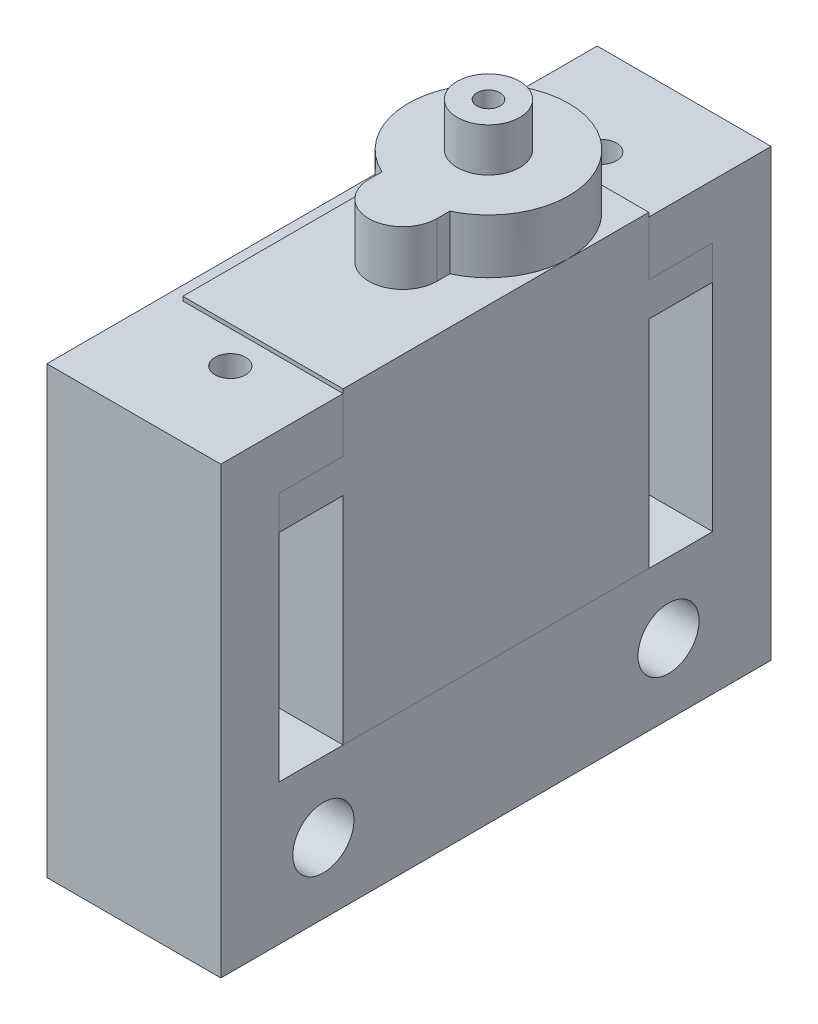
SolidWorks part; units mm, degrees
ref_plane "Plan de face" through (0, 0, 0) normal (0, 0, 1) x (1, 0, 0)
ref_plane "Plan de dessus" through (0, 0, 0) normal (0, 1, 0) x (1, 0, 0)
ref_plane "Plan de droite" through (0, 0, 0) normal (1, 0, 0) x (0, 0, -1)
sketch "Esquisse1" plane through (0, 0, 0) normal (1, 0, 0) x (0, 0, -1)
  line L0 (11.25, 0) -> (-11.25, 0) construction
  line L1 (0, 14.95) -> (0, -14.95) construction
  line L2 (-11.25, -14.95) -> (11.25, -14.95)
  line L3 (11.25, -14.95) -> (11.25, 0.95)
  line L4 (11.25, 0.95) -> (15.95, 0.95)
  line L5 (15.95, 0.95) -> (15.95, 3.45)
  line L6 (15.95, 3.45) -> (11.25, 3.45)
  line L7 (11.25, 3.45) -> (11.25, 7.75)
  line L8 (11.25, 7.75) -> (-11.25, 7.75)
  line L9 (-11.25, 7.75) -> (-11.25, 3.45)
  line L10 (-11.25, 3.45) -> (-15.95, 3.45)
  line L11 (-15.95, 3.45) -> (-15.95, 0.95)
  line L12 (-15.95, 0.95) -> (-11.25, 0.95)
  line L13 (-11.25, 0.95) -> (-11.25, -14.95)
  point P4 (0, 0)
  point P8 (0, 0)
  dimension "D1" = 15.9
  dimension "D2" = 2.5
  dimension "D3" = 4.7
  dimension "D4" = 22.5
  dimension "D5" = 4.7
  dimension "D6" = 4.3
  dimension "D7" = 2.5
  dimension "D8" = 15.9
  dimension "D9" = 22.5
  dimension "D10" = 18.4
  dimension "D11" = 22.7
extrude "Boss.-Extru.1" add sketch "Esquisse1" along normal blind 5.9 and the other way blind 5.9
sketch "Esquisse2" plane through (0, 7.75, 0) normal (0, 1, 0) x (1, 0, 0)
  line L0 (-5.9, 11.25) -> (5.9, 11.25) construction
  line L1 (-5.9, 11.25) -> (5.9, 11.25) construction
  line L2 (-2.5, 0.0058) -> (2.5, 0.0058) construction
  line L3 (0, 5.35) -> (0, -3.45) construction
  line L4 (-2.5, 0.0058) -> (-2.5, -3.45) construction
  line L5 (-2.5, -3.45) -> (2.5, -3.45) construction
  line L6 (2.5, -3.45) -> (2.5, 0.0058) construction
  line L7 (-2.5, -0.95) -> (-2.5, 0.0058)
  line L8 (2.5, -0.95) -> (2.5, 0.0058)
  arc A0 (2.5, 0.0058) -> (-2.5, 0.0058) centre (0, 5.35) ccw
  arc A1 (-2.5, -0.95) -> (2.5, -0.95) centre (0, -0.95) ccw
  point P6 (-2.5, -1.7221)
  point P11 (2.5, -1.7221)
extrude "Boss.-Extru.2" add sketch "Esquisse2" along normal blind 4
sketch "Esquisse3" plane through (0, 3.45, 0) normal (0, 1, 0) x (1, 0, 0)
  line L0 (0, 18.25) -> (0, 11.25) construction
  line L1 (0, 11.25) -> (7.0868, 11.25) construction
  line L2 (0, 15.95) -> (0, 13.65) construction
  line L3 (-5.9, 15.95) -> (5.9, 15.95) construction
  line L4 (-0.65, 15.95) -> (0.65, 15.95) construction
  line L5 (-0.65, 15.95) -> (-0.65, 14.4099)
  line L6 (0.65, 15.95) -> (0.65, 14.4099)
  line L7 (-0.65, 15.95) -> (0.65, 15.95)
  line L8 (0, 0) -> (11.6221, 0) construction
  line L9 (-0.65, -15.95) -> (0.65, -15.95) construction
  line L10 (0, -15.95) -> (0, -13.65) construction
  line L11 (0, -11.25) -> (7.0868, -11.25) construction
  line L12 (0, -18.25) -> (0, -11.25) construction
  line L13 (-0.65, -15.95) -> (0.65, -15.95)
  line L14 (0.65, -15.95) -> (0.65, -14.4099)
  line L15 (-0.65, -15.95) -> (-0.65, -14.4099)
  arc A0 (2.5, 0.0058) -> (-2.5, 0.0058) centre (0, 5.35) ccw construction
  arc A1 (-0.65, 14.4099) -> (0.65, 14.4099) centre (0, 13.65) ccw
  arc A2 (-0.65, -14.4099) -> (0.65, -14.4099) centre (0, -13.65) cw
  point P13 (0, 15.95)
  point P27 (0, -15.95)
extrude "Enlèv. mat.-Extru.1" cut sketch "Esquisse3" against normal up to surface (2.5 mm away) up to face at (0, 0.95, -13.6)
sketch "Esquisse4" plane through (0, 11.75, 0) normal (0, 1, 0) x (1, 0, 0)
  circle A0 centre (0, 5.35) radius 2.3
  circle A1 centre (0, 5.35) radius 0.85
extrude "Boss.-Extru.3" add sketch "Esquisse4" along normal blind 3.2
sketch "Sketch1" plane through (0, 3.45, 0) normal (0, 1, 0) x (1, 0, 0)
  line L0 (5.9, -11.25) -> (-5.9, -11.25)
  line L1 (5.9, -11.25) -> (5.9, -20.25)
  line L2 (-5.9, -11.25) -> (-5.9, -20.25)
  line L3 (5.9, -20.25) -> (-5.9, -20.25)
  circle A0 centre (0, -13.65) radius 1.125
  dimension "D2" = 2.25
  dimension "D1" = 9
extrude "Boss-Extrude1" add sketch "Sketch1" along normal blind 4 separate body
sketch "Sketch3" plane through (0, 3.45, 0) normal (0, -1, 0) x (1, 0, 0)
  line L1 (-5.9, 15.95) -> (5.9, 15.95)
  line L2 (-5.9, 15.95) -> (-5.9, 20.25)
  line L3 (-5.9, 20.25) -> (5.9, 20.25)
  line L4 (5.9, 15.95) -> (5.9, 20.25)
extrude "Boss-Extrude2" add sketch "Sketch3" along normal offset from surface (22.4 mm away) 4 separate body up to face at (0, -14.95, 0) offset beyond the face yes
sketch "Sketch4" plane through (0, -14.95, 0) normal (0, -1, 0) x (1, 0, 0)
  line L0 (-5.9, 0) -> (5.9, 0)
  line L1 (-5.9, 11.25) -> (5.9, 11.25)
  line L2 (-5.9, 11.25) -> (-5.9, -11.25)
  line L3 (-5.9, -11.25) -> (5.9, -11.25)
  line L4 (5.9, 11.25) -> (5.9, -11.25)
sketch "Sketch5" plane through (0, 0, 15.95) normal (0, 0, -1) x (-1, 0, 0)
  line L0 (5.9, -18.95) -> (5.9, 3.45) construction
  line L1 (-5.9, -18.95) -> (5.9, -18.95)
  line L2 (-5.9, -18.95) -> (-5.9, -14.95)
  line L3 (-5.9, -14.95) -> (5.9, -14.95)
  line L4 (5.9, -18.95) -> (5.9, -14.95)
  dimension "D1" = 4
extrude "Boss-Extrude3" add sketch "Sketch5" along normal up to vertex (15.95 mm away) separate body up to point (-5.9, -14.95, 0)
combine bodies "Combine1" operation type add bodies to combine 107 106 105
ref_plane "Plane1" through (0, 0, 0) normal (0, 0, -1) x (-1, 0, 0)
mirror "Mirror3" about plane through (0, 0, 0) normal (0, 0, -1) of "Boss-Extrude1", "Boss-Extrude2", "Boss-Extrude3"
sketch "Sketch6" plane through (0, -18.95, 0) normal (0, -1, 0) x (1, 0, 0)
  line L1 (-5.9, 20.25) -> (5.9, 20.25)
  line L2 (-5.9, 20.25) -> (-5.9, -20.25)
  line L3 (-5.9, -20.25) -> (5.9, -20.25)
  line L4 (5.9, 20.25) -> (5.9, -20.25)
extrude "Boss-Extrude4" add sketch "Sketch6" along normal blind 6.35
sketch "Sketch7" plane through (-5.9, 0, 0) normal (-1, 0, 0) x (0, 0, 1)
  line L0 (0, -25.3) -> (0, -14.95)
  line L1 (20.25, -25.3) -> (-20.25, -25.3) construction
  line L2 (11.25, -14.95) -> (-11.25, -14.95) construction
  line L3 (12.7, -20.125) -> (-12.7, -20.125)
  circle A0 centre (12.7, -20.125) radius 2.2479
  circle A1 centre (-12.7, -20.125) radius 2.2479
  point P9 (0, -20.125)
  dimension "D1" = 4.4958
  dimension "D2" = 25.4
extrude "Cut-Extrude1" cut sketch "Sketch7" against normal through all contours A0 | A1 region at (-5.9, -20.125, -14.8843) region at (-5.9, -17.9407, 12.7)
sketch "Sketch8" plane through (-5.9, 0, 0) normal (-1, 0, 0) x (0, 0, 1)
  line L1 (20.25, -25.3) -> (-20.25, -25.3)
  line L2 (20.25, -25.3) -> (20.25, 7.45)
  line L3 (20.25, 7.45) -> (-20.25, 7.45)
  line L4 (-20.25, -25.3) -> (-20.25, 7.45)
  circle A1 centre (-12.7, -20.125) radius 2.2479
  circle A3 centre (12.7, -20.125) radius 2.2479
  dimension "D1" = 4.4958
  dimension "D2" = 4.4958
extrude "Boss-Extrude5" add sketch "Sketch8" along normal blind 1
